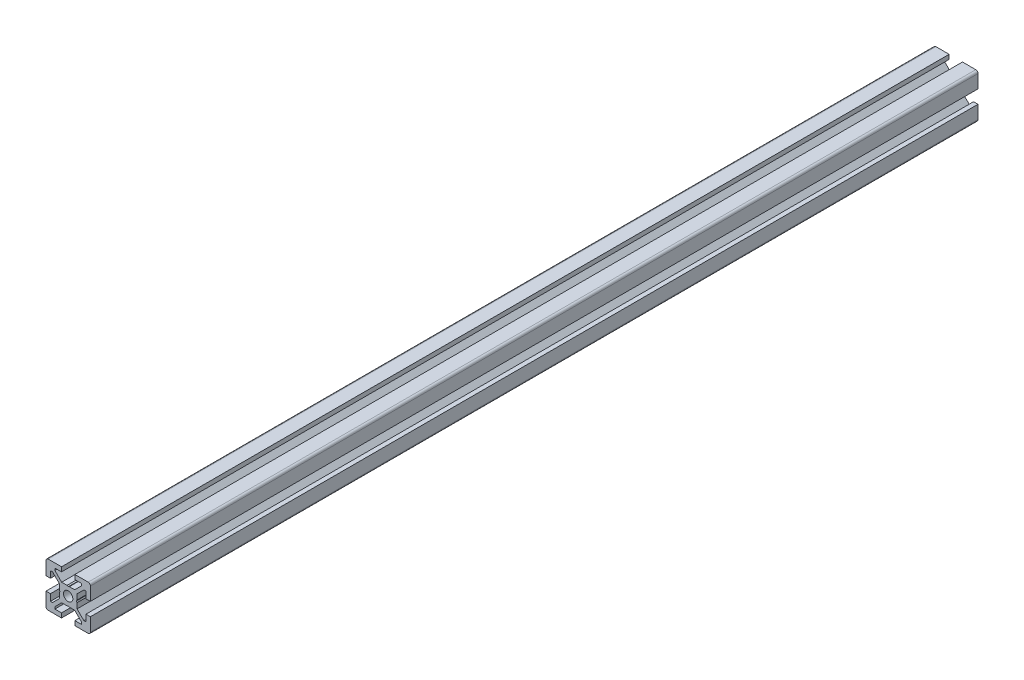
SolidWorks part; units mm, degrees
ref_plane "Front Plane" through (0, 0, 0) normal (0, 0, 1) x (1, 0, 0)
ref_plane "Top Plane" through (0, 0, 0) normal (0, 1, 0) x (1, 0, 0)
ref_plane "Right Plane" through (0, 0, 0) normal (1, 0, 0) x (0, 0, -1)
ref_plane "Plane1" through (0, 0, 0) normal (0, 0, 1) x (1, 0, 0)
sketch "Sketch1" plane through (0, 0, 0) normal (0, 0, 1) x (1, 0, 0)
  line L0 (-10, -3) -> (-10, -9)
  line L1 (-9, -10) -> (-3, -10)
  line L2 (-3, -10) -> (-3, -8)
  line L3 (-3, -8) -> (-6, -8)
  line L4 (-6, -8) -> (-6, -7.0607)
  line L5 (-6, -7.0607) -> (-2.9393, -4)
  line L6 (-2.9393, -4) -> (-0.5196, -4)
  line L7 (-0.5196, -4) -> (0, -3.7)
  line L8 (0, -3.7) -> (0.5196, -4)
  line L9 (0.5196, -4) -> (2.9393, -4)
  line L10 (2.9393, -4) -> (6, -7.0607)
  line L11 (6, -7.0607) -> (6, -8)
  line L12 (6, -8) -> (3, -8)
  line L13 (3, -8) -> (3, -10)
  line L14 (3, -10) -> (9, -10)
  line L15 (10, -9) -> (10, -3)
  line L16 (10, -3) -> (8, -3)
  line L17 (8, -3) -> (8, -6)
  line L18 (8, -6) -> (7.0607, -6)
  line L19 (7.0607, -6) -> (4, -2.9393)
  line L20 (4, -2.9393) -> (4, -0.5196)
  line L21 (4, -0.5196) -> (3.7, 0)
  line L22 (3.7, 0) -> (4, 0.5196)
  line L23 (4, 0.5196) -> (4, 2.9393)
  line L24 (4, 2.9393) -> (7.0607, 6)
  line L25 (7.0607, 6) -> (8, 6)
  line L26 (8, 6) -> (8, 3)
  line L27 (8, 3) -> (10, 3)
  line L28 (10, 3) -> (10, 9)
  line L29 (9, 10) -> (3, 10)
  line L30 (3, 10) -> (3, 8)
  line L31 (3, 8) -> (6, 8)
  line L32 (6, 8) -> (6, 7.0607)
  line L33 (6, 7.0607) -> (2.9393, 4)
  line L34 (2.9393, 4) -> (0.5196, 4)
  line L35 (0.5196, 4) -> (0, 3.7)
  line L36 (0, 3.7) -> (-0.5196, 4)
  line L37 (-0.5196, 4) -> (-2.9393, 4)
  line L38 (-2.9393, 4) -> (-6, 7.0607)
  line L39 (-6, 7.0607) -> (-6, 8)
  line L40 (-6, 8) -> (-3, 8)
  line L41 (-3, 8) -> (-3, 10)
  line L42 (-3, 10) -> (-9, 10)
  line L43 (-10, 9) -> (-10, 3)
  line L44 (-10, 3) -> (-8, 3)
  line L45 (-8, 3) -> (-8, 6)
  line L46 (-8, 6) -> (-7.0607, 6)
  line L47 (-7.0607, 6) -> (-4, 2.9393)
  line L48 (-4, 2.9393) -> (-4, 0.5196)
  line L49 (-4, 0.5196) -> (-3.7, 0)
  line L50 (-3.7, 0) -> (-4, -0.5196)
  line L51 (-4, -0.5196) -> (-4, -2.9393)
  line L52 (-4, -2.9393) -> (-7.0607, -6)
  line L53 (-7.0607, -6) -> (-8, -6)
  line L54 (-8, -6) -> (-8, -3)
  line L55 (-8, -3) -> (-10, -3)
  arc A0 (-10, -9) -> (-9, -10) centre (-9, -9) ccw
  arc A1 (9, -10) -> (10, -9) centre (9, -9) ccw
  arc A2 (10, 9) -> (9, 10) centre (9, 9) ccw
  arc A3 (-9, 10) -> (-10, 9) centre (-9, 9) ccw
extrude "Boss-Extrude1" add sketch "Sketch1" against normal blind 400
ref_plane "Plane2" through (0, 0, 0) normal (1, 0, 0) x (0, 0, -1)
sketch "Sketch2" plane through (0, 0, 0) normal (1, 0, 0) x (0, 0, -1)
  line L0 (0, 0) -> (0, 2.1)
  line L1 (0, 2.1) -> (400, 2.1)
  line L2 (400, 2.1) -> (400, 0)
  line L3 (400, 0) -> (0, 0)
  line L4 (400, 0) -> (0, 0) construction
revolve "Cut-Revolve1" cut sketch "Sketch2" angle 360 about L4 reverse direction yes
